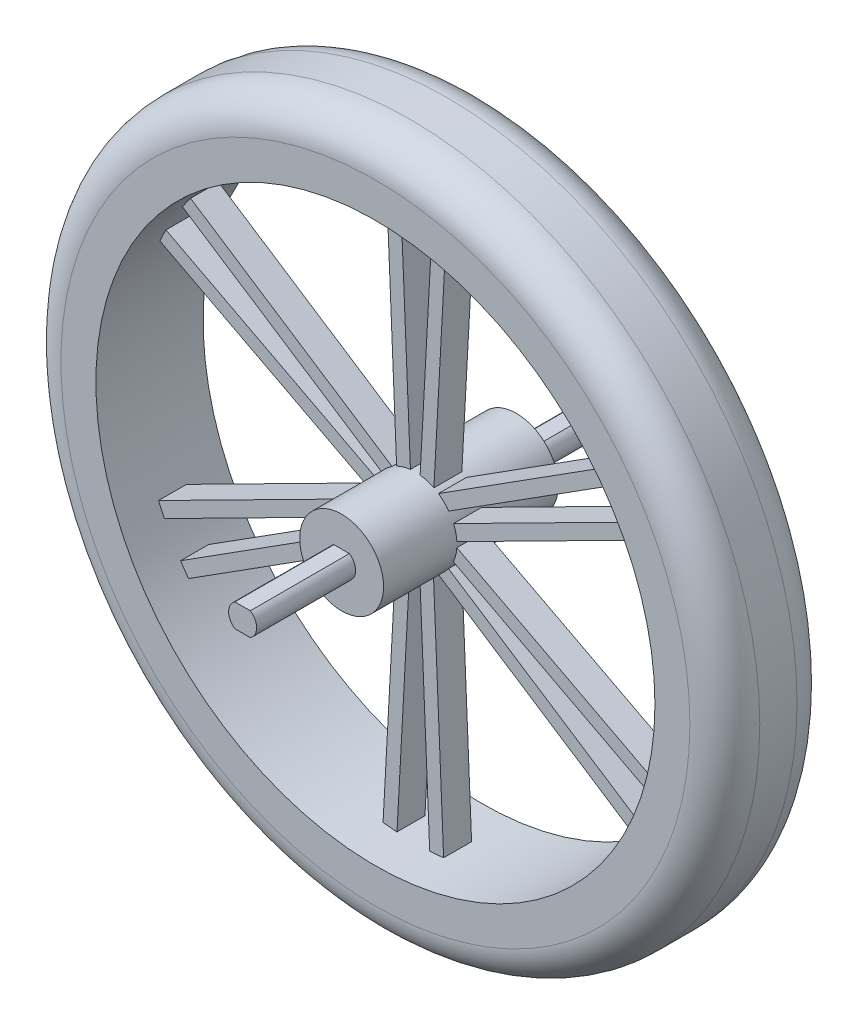
SolidWorks part; units mm, degrees
ref_plane "Front Plane" through (0, 0, 0) normal (0, 0, 1) x (1, 0, 0)
ref_plane "Top Plane" through (0, 0, 0) normal (0, 1, 0) x (1, 0, 0)
ref_plane "Right Plane" through (0, 0, 0) normal (1, 0, 0) x (0, 0, -1)
sketch "Sketch1" plane through (0, 0, 0) normal (0, 0, 1) x (1, 0, 0)
  circle A0 centre (0, 0) radius 18
  dimension "D1" = 36
extrude "Boss-Extrude1" add sketch "Sketch1" along normal mid plane 75
sketch "Sketch2" plane through (0, 0, 0) normal (0, 0, 1) x (1, 0, 0)
  circle A0 centre (0, 0) radius 150
  circle A1 centre (0, 0) radius 120
  dimension "D1" = 300
  dimension "D2" = 30
extrude "Boss-Extrude2" add sketch "Sketch2" along normal mid plane 46 separate body
sketch "Sketch3" plane through (0, 0, 0) normal (0, 0, 1) x (1, 0, 0)
  line L0 (-6.293, 119.8349) -> (-1.9699, 17.8919)
  line L3 (-12.2787, 119.3702) -> (-7.9024, 16.1726)
  line L4 (13.7209, 119.213) -> (8.0973, 16.0759)
  line L5 (2.1861, 17.8668) -> (7.7412, 119.75)
  circle A0 centre (0, 0) radius 18 construction
  circle A1 centre (0, 0) radius 120 construction
  arc A8 (13.7209, 119.213) -> (7.7412, 119.75) centre (0, 0) ccw
  arc A9 (8.0973, 16.0759) -> (2.1861, 17.8668) centre (0, 0) ccw
  arc A10 (-6.293, 119.8349) -> (-12.2787, 119.3702) centre (0, 0) ccw
  arc A11 (-1.9699, 17.8919) -> (-7.9024, 16.1726) centre (0, 0) ccw
  dimension "D1" = 26
  dimension "D2" = 6
  dimension "D3" = 16
extrude "Boss-Extrude3" add sketch "Sketch3" along normal mid plane 12
ref_axis "Axis2" through (0, 0, -53.35) along (0, 0, 1)
pattern_circular "CirPattern15" count 6 over 360 about axis through (0, 0, -53.35) along (0, 0, 1) of "Boss-Extrude3"
fillet "Fillet1" radius 15 2 edges at (150, 0, -23) (150, 0, 23)
sketch "Sketch5" plane through (0, 0, 37.5) normal (0, 0, 1) x (1, 0, 0)
  line L0 (-3.3166, 5) -> (3.3166, 5)
  line L1 (-3.3166, -5) -> (3.3166, -5)
  arc A0 (-3.3166, 5) -> (-3.3166, -5) centre (0, 0) ccw
  arc A1 (3.3166, -5) -> (3.3166, 5) centre (0, 0) ccw
  dimension "D1" = 12
  dimension "D2" = 10
extrude "Boss-Extrude4" add sketch "Sketch5" along normal blind 42.5
mirror "Mirror1" about plane through (0, 0, 0) normal (0, 0, 1) of "Boss-Extrude4"
